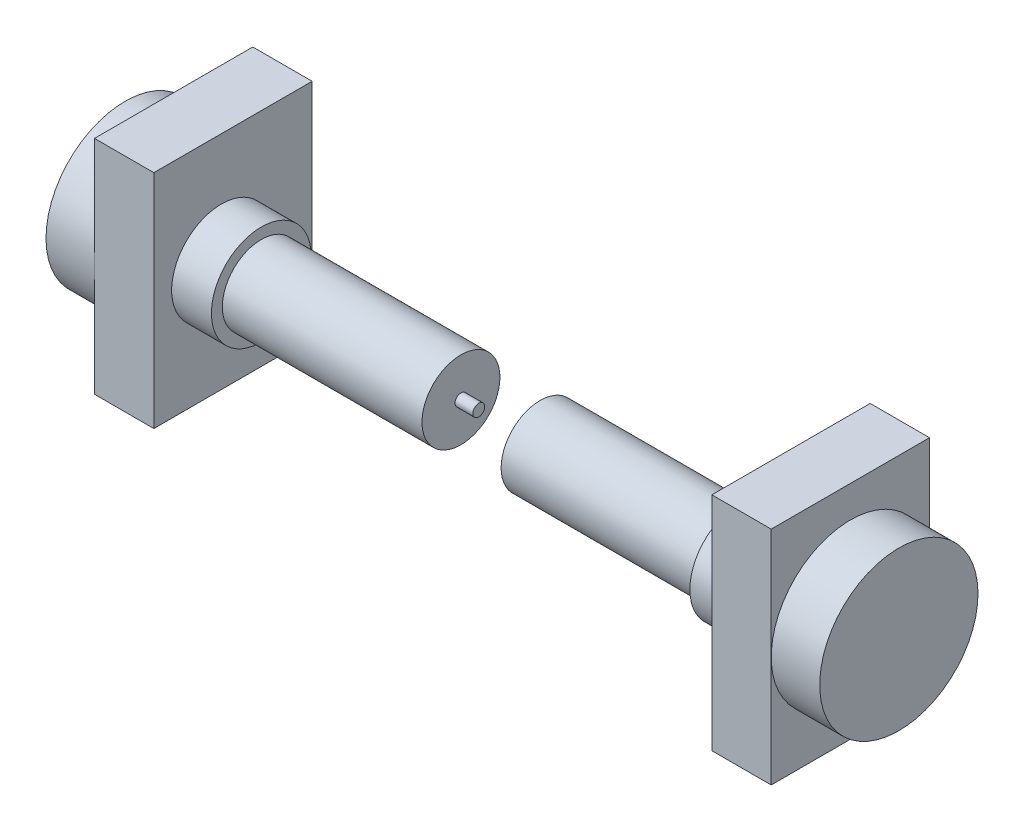
SolidWorks part; units mm, degrees
ref_plane "Plan de face" through (0, 0, 0) normal (0, 0, 1) x (1, 0, 0)
ref_plane "Plan de dessus" through (0, 0, 0) normal (0, 1, 0) x (1, 0, 0)
ref_plane "Plan de droite" through (0, 0, 0) normal (1, 0, 0) x (0, 0, -1)
sketch "Esquisse2" plane through (0, 0, 6) normal (0, 0, 1) x (1, 0, 0)
  line L0 (-85.5, -28) -> (85.5, -28) construction
  line L1 (-85.5, 28) -> (-70.5, 28)
  line L2 (-85.5, 28) -> (-85.5, -28)
  line L3 (-85.5, -28) -> (-70.5, -28)
  line L4 (-70.5, 28) -> (-70.5, -28)
  dimension "D1" = 15
extrude "Enlèv. mat.-Extru.1" cut sketch "Esquisse2" against normal blind 3 rebuild error yes
sketch "Esquisse3" plane through (0, 0, 6) normal (0, 0, 1) x (1, 0, 0)
  line L0 (-70.5, -28) -> (85.5, -28) construction
  line L1 (85.5, 28) -> (70.5, 28)
  line L2 (85.5, 28) -> (85.5, -28)
  line L3 (85.5, -28) -> (70.5, -28)
  line L4 (70.5, 28) -> (70.5, -28)
  dimension "D1" = 15
extrude "Enlèv. mat.-Extru.2" cut sketch "Esquisse3" against normal blind 3 rebuild error yes
sketch "Esquisse4" plane through (0, 0, 3) normal (0, 0, 1) x (1, 0, 0)
  line L1 (-85.5, 28) -> (-70.5, 28)
  line L2 (-85.5, 28) -> (-85.5, -28)
  line L3 (-85.5, -28) -> (-70.5, -28)
  line L4 (-70.5, 28) -> (-70.5, -28)
  line L5 (85.5, 28) -> (70.5, 28)
  line L6 (85.5, 28) -> (85.5, -28)
  line L7 (85.5, -28) -> (70.5, -28)
  line L8 (70.5, 28) -> (70.5, -28)
extrude "Boss.-Extru.2" add sketch "Esquisse4" along normal blind 40
sketch "Esquisse5" plane through (-85.5, 0, 0) normal (-1, 0, 0) x (0, 0, 1)
  circle A0 centre (23, 0) radius 20
extrude "Boss.-Extru.3" add sketch "Esquisse5" along normal blind 12.25
sketch "Esquisse6" plane through (85.5, 0, 0) normal (1, 0, 0) x (0, 0, -1)
  circle A0 centre (-23, 0) radius 20
extrude "Boss.-Extru.4" add sketch "Esquisse6" along normal blind 12.25
sketch "Esquisse7" plane through (70.5, 0, 0) normal (-1, 0, 0) x (0, 0, 1)
  line L0 (43, 28) -> (43, -28) construction
  circle A0 centre (25.9, 0) radius 12.6
  point P2 (43, 0)
  dimension "D1" = 17.1
extrude "Boss.-Extru.5" add sketch "Esquisse7" along normal blind 10.05
sketch "Esquisse9" plane through (-70.5, 0, 0) normal (1, 0, 0) x (0, 0, -1)
  line L0 (-43, -28) -> (-43, 28) construction
  circle A0 centre (-25.9, 0) radius 12.6
  dimension "D1" = 17.1
extrude "Boss.-Extru.6" add sketch "Esquisse9" along normal blind 10.05
sketch "Esquisse11" plane through (60.45, 0, 0) normal (-1, 0, 0) x (0, 0, 1)
  circle A0 centre (25.9, 0) radius 9.85
extrude "Boss.-Extru.7" add sketch "Esquisse11" along normal blind 50.45
sketch "Esquisse12" plane through (-60.45, 0, 0) normal (1, 0, 0) x (0, 0, -1)
  circle A0 centre (-25.9, 0) radius 9.85
extrude "Boss.-Extru.8" add sketch "Esquisse12" along normal blind 50.45
sketch "Esquisse13" plane through (-10, 0, 0) normal (1, 0, 0) x (0, 0, -1)
  circle A0 centre (-25.9, 0) radius 1.5
extrude "Boss.-Extru.9" add sketch "Esquisse13" along normal blind 4.5
sketch "Esquisse14" plane through (10, 0, 0) normal (-1, 0, 0) x (0, 0, 1)
  circle A0 centre (25.9, 0) radius 1.5
extrude "Boss.-Extru.10" add sketch "Esquisse14" along normal blind 4.5
